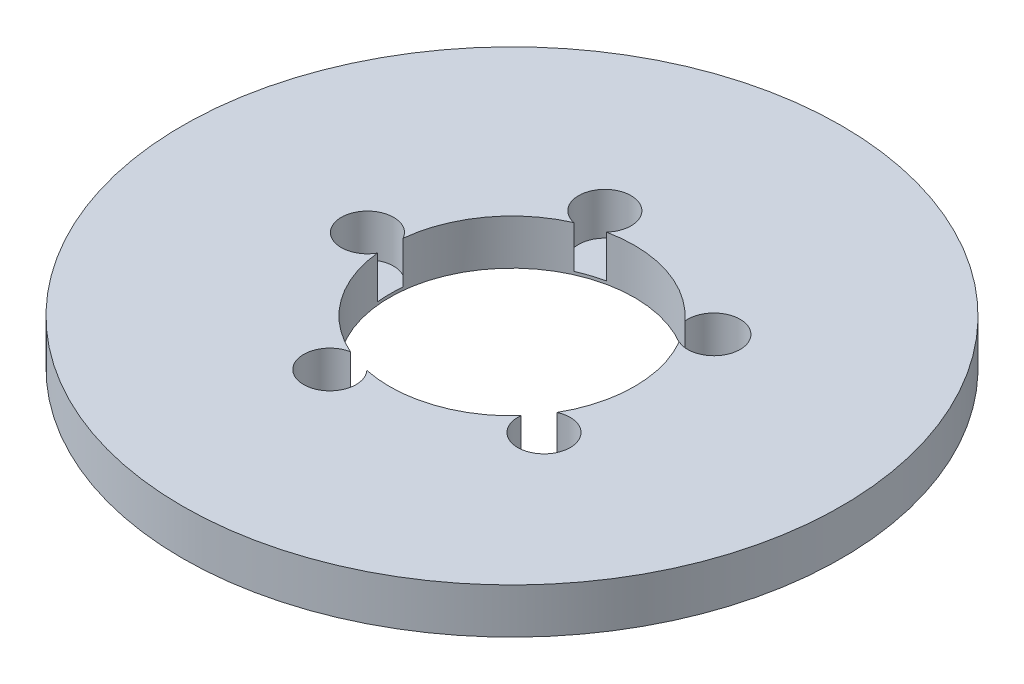
SolidWorks part; units mm, degrees
ref_plane "Front Plane" through (0, 0, 0) normal (0, 0, 1) x (1, 0, 0)
ref_plane "Top Plane" through (0, 0, 0) normal (0, 1, 0) x (1, 0, 0)
ref_plane "Right Plane" through (0, 0, 0) normal (1, 0, 0) x (0, 0, -1)
sketch "Sketch1" plane through (0, 0, 0) normal (0, 1, 0) x (1, 0, 0)
  circle A0 centre (0, 0) radius 87.5
  dimension "FLANGE_OD" = 175
extrude "Boss-Extrude1" add sketch "Sketch1" along normal blind 12
sketch "Sketch2" plane through (0, 0, 0) normal (0, 1, 0) x (1, 0, 0)
  circle A0 centre (0, 0) radius 32.5
  dimension "BORE_D" = 65
extrude "Cut-Extrude1" cut sketch "Sketch2" along normal through all
sketch "Sketch3" plane through (0, 12, 0) normal (0, 1, 0) x (1, 0, 0)
  circle A0 centre (0, 0) radius 38.3807 construction
  circle A1 centre (-38.3807, 0) radius 6.9605
  dimension "BOLT_D" = 13.9211
  dimension "BOLT_PCD" = 76.7613
extrude "Cut-Extrude2" cut sketch "Sketch3" against normal blind 11.2287
pattern_circular "CirPattern1" count 5 over 360 about axis through (0, 0, 0) along (0, 1, 0) of "Cut-Extrude2"
